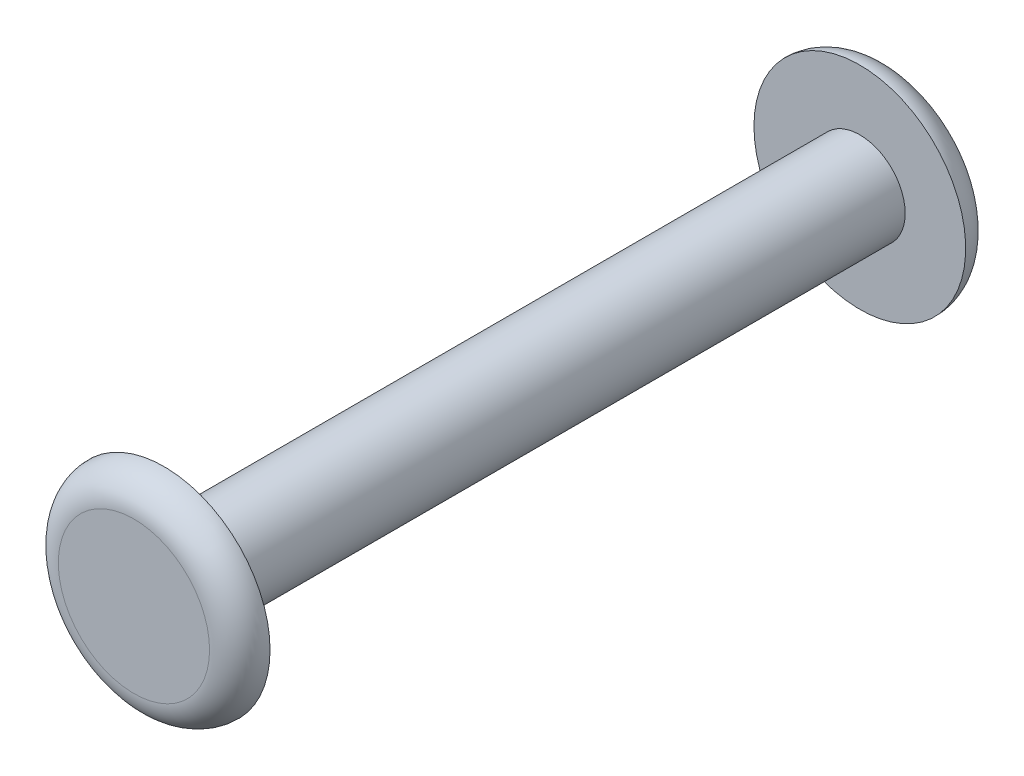
SolidWorks part; units mm, degrees
ref_plane "Front Plane" through (0, 0, 0) normal (0, 0, 1) x (1, 0, 0)
ref_plane "Top Plane" through (0, 0, 0) normal (0, 1, 0) x (1, 0, 0)
ref_plane "Right Plane" through (0, 0, 0) normal (1, 0, 0) x (0, 0, -1)
sketch "Sketch1" plane through (0, 0, 0) normal (0, 0, 1) x (1, 0, 0)
  circle A0 centre (0, 0) radius 3.75
  dimension "D1" = 7.5
extrude "Boss-Extrude1" add sketch "Sketch1" along normal mid plane 57.5
sketch "Sketch2" plane through (0, 0, 28.75) normal (0, 0, 1) x (1, 0, 0)
  circle A0 centre (0, 0) radius 3.75 construction
  circle A1 centre (0, 0) radius 3.75
  circle A2 centre (0, 0) radius 8.75
  circle M3 centre (0, 0) radius 3.75
  dimension "D1" = 5
extrude "Boss-Extrude2" add sketch "Sketch2" along normal blind 2.5 contours M3 | A2 M3 region at (0, 0, 28.75) region at (-8.5025, 0, 28.75)
sketch "Sketch3" plane through (0, 0, -28.75) normal (0, 0, -1) x (-1, 0, 0)
  circle A2 centre (0, 0) radius 8.75
  circle A3 centre (0, 0) radius 8.75
  dimension "D1" = 5
extrude "Boss-Extrude3" add sketch "Sketch3" along normal blind 2.5
fillet "Fillet1" radius 2.5 2 edges at (-8.75, 0, -31.25) (8.75, 0, 31.25)
